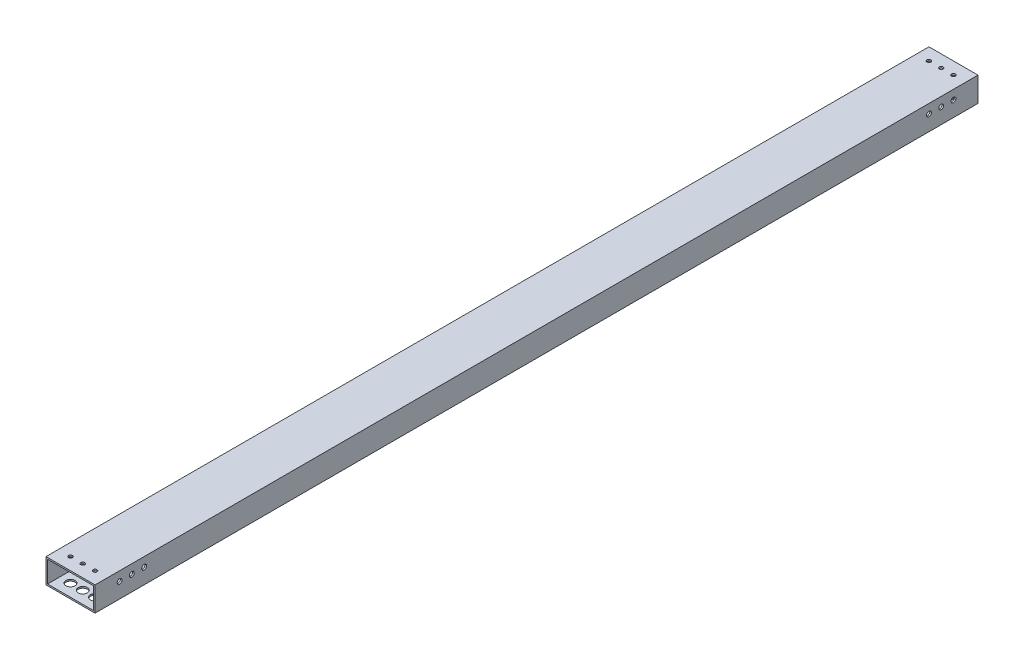
SolidWorks part; units mm, degrees
other "Markup1"
sketch "Sketch5" plane through (-25.4, -12.7, -457.2) normal (-0.35, -0.9329, -0.0852) x (-0.8023, 0.2515, 0.5413)
sketch "Sketch6" plane through (-25.4, -12.7, -457.2) normal (-0.35, -0.9329, -0.0852) x (-0.8023, 0.2515, 0.5413)
sketch "Sketch8" plane through (-25.4, -12.7, -457.2) normal (-0.35, -0.9329, -0.0852) x (-0.8023, 0.2515, 0.5413)
material "6061-T6 (SS)"
ref_plane "Front Plane" through (0, 0, 0) normal (0, 0, 1) x (1, 0, 0)
ref_plane "Top Plane" through (0, 0, 0) normal (0, 1, 0) x (1, 0, 0)
ref_plane "Right Plane" through (0, 0, 0) normal (1, 0, 0) x (0, 0, -1)
sketch "Sketch1" plane through (0, 0, 0) normal (0, 0, 1) x (1, 0, 0)
  line L0 (-23.8125, 11.1125) -> (23.8125, 11.1125)
  line L1 (-25.4, -12.7) -> (25.4, -12.7)
  line L2 (-25.4, -12.7) -> (-25.4, 12.7)
  line L3 (-25.4, 12.7) -> (25.4, 12.7)
  line L4 (25.4, -12.7) -> (25.4, 12.7)
  line L5 (-25.4, -12.7) -> (25.4, 12.7) construction
  line L6 (-25.4, 12.7) -> (25.4, -12.7) construction
  line L7 (23.8125, -11.1125) -> (23.8125, 11.1125)
  line L8 (-23.8125, -11.1125) -> (23.8125, -11.1125)
  line L9 (-23.8125, -11.1125) -> (-23.8125, 11.1125)
  point P0 (0, 0)
  dimension "D1" = 50.8
  dimension "D2" = 25.4
  dimension "D3" = 1.5875
extrude "Boss-Extrude1" add sketch "Sketch1" along normal mid plane 914.4
sketch "Sketch3" plane through (0, 12.7, 0) normal (0, 1, 0) x (1, 0, 0)
  line L2 (25.4, -457.2) -> (-25.4, -457.2) construction
  line L3 (25.4, 0) -> (-25.4, 0) construction
  line L4 (25.4, -457.2) -> (25.4, 457.2) construction
  line L5 (-25.4, -457.2) -> (-25.4, 457.2) construction
  circle A0 centre (0, -444.5) radius 2.0193
  circle A1 centre (12.7, -444.5) radius 2.0193
  circle A2 centre (-12.7, -444.5) radius 2.0193
  circle A3 centre (12.7, 444.5) radius 2.0193
  circle A4 centre (0, 444.5) radius 2.0193
  circle A5 centre (-12.7, 444.5) radius 2.0193
  dimension "D1" = 4.0386
  dimension "D2" = 12.7
  dimension "D3" = 12.7
  dimension "D4" = 12.7
extrude "Cut-Extrude2" cut sketch "Sketch3" against normal up to surface (1.5875 mm away) up to face at (0, 11.1125, 0)
sketch "Sketch4" plane through (0, -12.7, 0) normal (0, -1, 0) x (1, 0, 0)
  circle A0 centre (-12.7, 444.5) radius 2.0193 construction
  circle A1 centre (0, 444.5) radius 2.0193 construction
  circle A2 centre (12.7, 444.5) radius 2.0193 construction
  circle A3 centre (-12.7, 444.5) radius 2.0193
  circle A4 centre (0, 444.5) radius 2.0193
  circle A5 centre (12.7, 444.5) radius 2.0193
  circle A6 centre (-12.7, -444.5) radius 2.0193 construction
  circle A7 centre (0, -444.5) radius 2.0193 construction
  circle A8 centre (12.7, -444.5) radius 2.0193 construction
  circle A9 centre (-12.7, -444.5) radius 2.0193
  circle A10 centre (0, -444.5) radius 2.0193
  circle A11 centre (12.7, -444.5) radius 2.0193
  circle A12 centre (-12.7, 444.5) radius 4.7625
  circle A13 centre (0, 444.5) radius 4.7625
  circle A14 centre (12.7, 444.5) radius 4.7625
  circle A15 centre (-12.7, -444.5) radius 4.7625
  circle A16 centre (0, -444.5) radius 4.7625
  circle A17 centre (12.7, -444.5) radius 4.7625
  dimension "D1" = 9.525
  dimension "D2" = 9.525
extrude "Cut-Extrude4" cut sketch "Sketch4" against normal up to surface (1.5875 mm away) contours A12 A3 | A13 A4 | A4 | A3 | A5 | A14 A5 | A11 | A17 A11 | A16 A10 | A10 | A15 A9 | A9 region at (-12.7, -12.7, 444.5) region at (0, -12.7, 444.5) region at (12.7, -12.7, 444.5) region at (-12.7, -12.7, -444.5) region at (0, -12.7, -444.5) region at (12.7, -12.7, -444.5) region at (-17.3278, -12.7, 444.5) region at (-4.6278, -12.7, 444.5) region at (8.0722, -12.7, 444.5) region at (-17.3278, -12.7, -444.5) region at (-4.6278, -12.7, -444.5) region at (8.0722, -12.7, -444.5) up to face at (0, -11.1125, 0)
sketch "Sketch7" plane through (25.4, 0, 0) normal (1, 0, 0) x (0, 0, -1)
  line L0 (-457.2, -12.7) -> (-457.2, 12.7) construction
  line L1 (-457.2, 12.7) -> (457.2, 12.7) construction
  line L2 (0, 12.7) -> (0, -12.7) construction
  line L3 (-457.2, -12.7) -> (457.2, -12.7) construction
  circle A0 centre (-444.5, 3.175) radius 2.4892
  circle A1 centre (-431.8, 3.175) radius 2.4892
  circle A2 centre (-419.1, 3.175) radius 2.4892
  circle A3 centre (-406.4, 3.175) radius 2.4892
  circle A4 centre (406.4, 3.175) radius 2.4892
  circle A5 centre (419.1, 3.175) radius 2.4892
  circle A6 centre (431.8, 3.175) radius 2.4892
  circle A7 centre (444.5, 3.175) radius 2.4892
  dimension "D3" = 4.9784
  dimension "D1" = 12.7
  dimension "D2" = 9.525
  dimension "D4" = 12.7
  dimension "D5" = 12.7
  dimension "D6" = 12.7
extrude "Cut-Extrude5" cut sketch "Sketch7" against normal through all contours A1 | A2 | A3 | A5 | A4 | A6 region at (25.4, 3.175, 431.8) region at (25.4, 3.175, 419.1) region at (25.4, 3.175, 406.4) region at (25.4, 3.175, -406.4) region at (25.4, 3.175, -419.1) region at (25.4, 3.175, -431.8)
